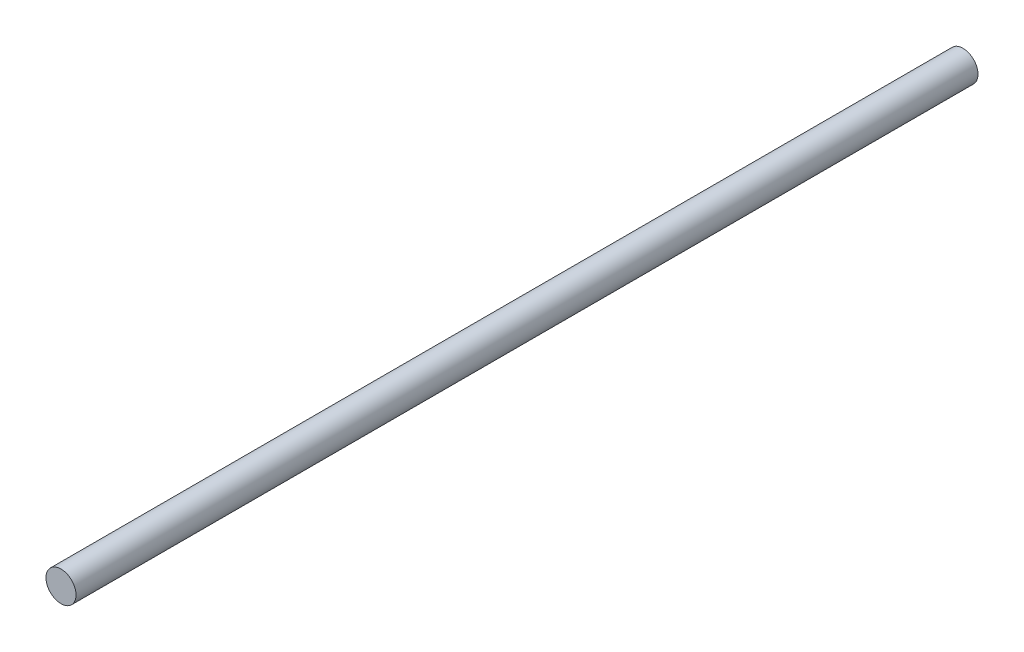
SolidWorks part; units mm, degrees
ref_plane "Front Plane" through (0, 0, 0) normal (0, 0, 1) x (1, 0, 0)
ref_plane "Top Plane" through (0, 0, 0) normal (0, 1, 0) x (1, 0, 0)
ref_plane "Right Plane" through (0, 0, 0) normal (1, 0, 0) x (0, 0, -1)
sketch "Sketch1" plane through (0, 0, 0) normal (0, 0, 1) x (1, 0, 0)
  circle A0 centre (0, 0) radius 3.175
  dimension "D1" = 6.35
extrude "Boss-Extrude1" add sketch "Sketch1" along normal blind 190.5
